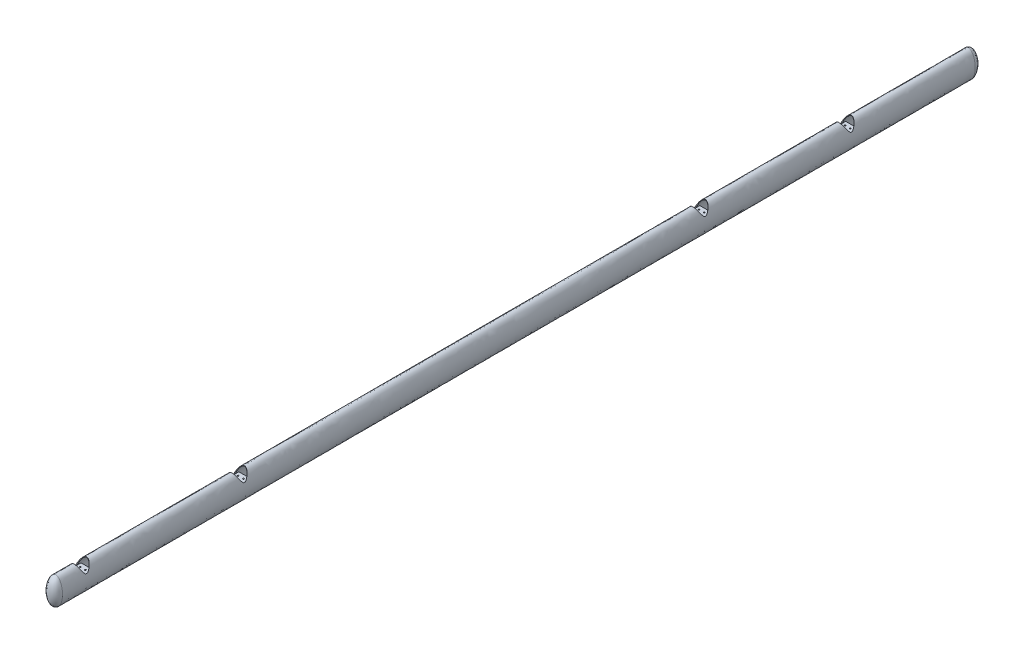
SolidWorks part; units mm, degrees
material "6061 Сплав"
ref_plane "Спереди" through (0, 0, 0) normal (0, 0, 1) x (1, 0, 0)
ref_plane "Сверху" through (0, 0, 0) normal (0, 1, 0) x (1, 0, 0)
ref_plane "Справа" through (0, 0, 0) normal (1, 0, 0) x (0, 0, -1)
sketch "Эскиз1" plane through (0, 0, 0) normal (0, 0, 1) x (1, 0, 0)
  line L0 (0, 286.5014) -> (0, -276.3874) construction
  ellipse E0 centre (234.2877, 0) end of major axis (234.2877, -30) minor radius 15
  ellipse E3 centre (234.2877, 0) end of major axis (234.2877, 28.8) minor radius 13.8
  dimension "D5" = 234.2877
extrude "Бобышка-Вытянуть1" add sketch "Эскиз1" along normal blind 2000
ref_plane "Плоскость1" through (0, 30, 0) normal (0, 1, 0) x (1, 0, 0)
sketch "Эскиз3" plane through (0, 30, 0) normal (0, 1, 0) x (1, 0, 0)
  circle A0 centre (-234.2877, -1946) radius 13.85
  circle A4 centre (234.2877, -270) radius 13.85
  circle A5 centre (234.2877, -590) radius 13.85
  circle A6 centre (234.2877, -1600) radius 13.85
  circle A7 centre (234.2877, -1946) radius 13.85
extrude "Вырез-Вытянуть1" cut sketch "Эскиз3" against normal blind 18
ref_plane "Плоскость2" through (234.2877, 0, 0) normal (1, 0, 0) x (0, 0, -1)
sketch "Эскиз4" plane through (234.2877, 0, 0) normal (1, 0, 0) x (0, 0, -1)
  line L0 (103.9999, 0) -> (-2069.6798, 0) construction
  line L1 (-1613.85, 30) -> (-1932.15, 30) construction
  line L2 (-1959.85, 12) -> (-1931.85, 12)
  line L3 (-1959.85, 12) -> (-1959.85, 8)
  line L4 (-1959.85, 8) -> (-1931.85, 8)
  line L5 (-1931.85, 12) -> (-1931.85, 8)
  line L6 (-1959.85, 30) -> (-1959.85, -38.8491) construction
  line L7 (-1586.15, 30) -> (-1586.15, -17.8904) construction
  line L8 (-603.85, 30) -> (-603.85, -10.0051) construction
  line L10 (-256.15, 30) -> (-256.15, -10.0051) construction
  line L11 (-1614.15, 12) -> (-1586.15, 12)
  line L12 (-1614.15, 12) -> (-1614.15, 8)
  line L13 (-1614.15, 8) -> (-1586.15, 8)
  line L14 (-1586.15, 12) -> (-1586.15, 8)
  line L15 (-603.85, 12) -> (-575.85, 12)
  line L16 (-603.85, 12) -> (-603.85, 8)
  line L17 (-603.85, 8) -> (-575.85, 8)
  line L18 (-575.85, 12) -> (-575.85, 8)
  line L19 (-283.85, 30) -> (-576.15, 30) construction
  line L20 (-284.15, 12) -> (-256.15, 12)
  line L21 (-284.15, 12) -> (-284.15, 8)
  line L22 (-284.15, 8) -> (-256.15, 8)
  line L23 (-256.15, 12) -> (-256.15, 8)
  dimension "D1" = 18
  dimension "D2" = 4
  dimension "D3" = 28
  dimension "D4" = 4
  dimension "D5" = 28
  dimension "D6" = 8
  dimension "D7" = 4
  dimension "D8" = 28
  dimension "D9" = 18
  dimension "D10" = 4
  dimension "D11" = 28
  dimension "D12" = 18
extrude "Бобышка-Вытянуть2" add sketch "Эскиз4" along normal up to next and the other way up to next
sketch3d "Трехмерный эскиз1"
  line L0 (0, 0, 0) -> (0, 0, 781.8375) construction
sketch "Эскиз6" plane through (0, 12, 0) normal (0, 1, 0) x (1, 0, 0)
  line L0 (207.6556, -1946) -> (272.459, -1946) construction
  line L1 (234.2877, -1946) -> (234.2877, -1918.1086) construction
  line L2 (228.6309, -1940.3431) -> (228.6309, -1951.6569) construction
  line L7 (239.9446, -1951.6569) -> (228.6309, -1940.3431) construction
  line L8 (239.9446, -1940.3431) -> (228.6309, -1951.6569) construction
  line L9 (228.6309, -1951.6569) -> (239.9446, -1951.6569) construction
  line L10 (239.9446, -1951.6569) -> (239.9446, -1940.3431) construction
  line L11 (239.9446, -1940.3431) -> (228.6309, -1940.3431) construction
  line L12 (234.2877, -1918.1086) -> (234.2877, 319.955) construction
  line L13 (234.2877, -50) -> (234.2877, 50) construction
  line L15 (234.2877, -1600) -> (234.2877, -1572.1086) construction
  line L16 (228.6309, -1594.3431) -> (228.6309, -1605.6569) construction
  line L17 (239.9446, -1605.6569) -> (228.6309, -1594.3431) construction
  line L18 (239.9446, -1594.3431) -> (228.6309, -1605.6569) construction
  line L19 (228.6309, -1605.6569) -> (239.9446, -1605.6569) construction
  line L20 (239.9446, -1605.6569) -> (239.9446, -1594.3431) construction
  line L21 (239.9446, -1594.3431) -> (228.6309, -1594.3431) construction
  line L22 (234.2877, -590) -> (234.2877, -571.5378) construction
  line L23 (228.6309, -584.3431) -> (228.6309, -595.6569) construction
  line L24 (239.9446, -595.6569) -> (228.6309, -584.3431) construction
  line L25 (239.9446, -584.3431) -> (228.6309, -595.6569) construction
  line L26 (228.6309, -595.6569) -> (239.9446, -595.6569) construction
  line L27 (239.9446, -595.6569) -> (239.9446, -584.3431) construction
  line L28 (239.9446, -584.3431) -> (228.6309, -584.3431) construction
  line L29 (234.2877, -270) -> (234.2877, -258.9739) construction
  line L30 (228.6309, -264.3431) -> (228.6309, -275.6569) construction
  line L31 (239.9446, -275.6569) -> (228.6309, -264.3431) construction
  line L32 (239.9446, -264.3431) -> (228.6309, -275.6569) construction
  line L33 (228.6309, -275.6569) -> (239.9446, -275.6569) construction
  line L34 (239.9446, -275.6569) -> (239.9446, -264.3431) construction
  line L35 (239.9446, -264.3431) -> (228.6309, -264.3431) construction
  arc A0 (248.0355, -1944.32) -> (220.54, -1944.32) centre (234.2877, -1946) ccw construction
  circle A1 centre (228.6309, -1940.3431) radius 1.5
  circle A2 centre (239.9446, -1940.3431) radius 1.5
  circle A3 centre (228.6309, -1951.6569) radius 1.5
  circle A4 centre (239.9446, -1951.6569) radius 1.5
  circle A5 centre (228.6309, -1594.3431) radius 1.5
  circle A6 centre (239.9446, -1594.3431) radius 1.5
  circle A7 centre (228.6309, -1605.6569) radius 1.5
  circle A8 centre (239.9446, -1605.6569) radius 1.5
  circle A9 centre (228.6309, -584.3431) radius 1.5
  circle A10 centre (239.9446, -584.3431) radius 1.5
  circle A11 centre (228.6309, -595.6569) radius 1.5
  circle A12 centre (239.9446, -595.6569) radius 1.5
  circle A13 centre (228.6309, -264.3431) radius 1.5
  circle A14 centre (239.9446, -264.3431) radius 1.5
  circle A15 centre (228.6309, -275.6569) radius 1.5
  circle A16 centre (239.9446, -275.6569) radius 1.5
  point P16 (234.2877, -590)
  point P20 (234.2877, -270)
  point P31 (234.2877, -1600)
  dimension "D3" = 3
  dimension "D5" = 3
  dimension "D7" = 3
  dimension "D9" = 3
  dimension "D1" = 0
  dimension "D2" = 16
  dimension "D4" = 16
  dimension "D6" = 16
  dimension "D8" = 16
extrude "Вырез-Вытянуть2" cut sketch "Эскиз6" against normal through all
sketch "Эскиз7" plane through (0, 0, 2000) normal (0, 0, 1) x (1, 0, 0)
  line L1 (234.2877, -50) -> (234.2877, 50) construction
  line L2 (234.2877, 30) -> (234.2877, 28.8)
  line L3 (234.2877, -28.8) -> (234.2877, -30)
  ellipse E0 centre (234.2877, 0) end of major axis (234.2877, 28.8) minor radius 13.8 (234.2877, -28.8) -> (234.2877, 28.8) ccw
  ellipse E2 centre (234.2877, 0) end of major axis (234.2877, 28.8) minor radius 13.8 construction
  ellipse E3 centre (234.2877, 0) end of major axis (234.2877, 30) minor radius 15 (234.2877, -30) -> (234.2877, 30) ccw
  ellipse E4 centre (234.2877, 0) end of major axis (234.2877, 30) minor radius 15 construction
  point P0 (234.2877, 0)
sketch3d "Трехмерный эскиз2"
  line L0 (234.2877, 30, 2000) -> (234.2877, -43.8, 2000) construction
revolve "Повернуть1" add sketch "Эскиз7" angle 180 about L0
sketch "Эскиз8" plane through (0, 0, 0) normal (0, 0, -1) x (-1, 0, 0)
  line L0 (-234.2877, 30) -> (-234.2877, -43.8) construction
  line L1 (-234.2877, 30) -> (-234.2877, 28.8)
  line L2 (-234.2877, -28.8) -> (-234.2877, -30)
  ellipse E0 centre (-234.2877, 0) end of major axis (-234.2877, 28.8) minor radius 13.8 (-234.2877, -28.8) -> (-234.2877, 28.8) ccw
  ellipse E1 centre (-234.2877, 0) end of major axis (-234.2877, 28.8) minor radius 13.8 construction
  ellipse E2 centre (-234.2877, 0) end of major axis (-234.2877, 28.8) minor radius 13.8 (-234.2877, -28.8) -> (-234.2877, 28.8) ccw construction
  ellipse E3 centre (-234.2877, 0) end of major axis (-234.2877, 30) minor radius 15 (-234.2877, -30) -> (-234.2877, 30) ccw
  ellipse E4 centre (-234.2877, 0) end of major axis (-234.2877, 30) minor radius 15 construction
  point P0 (-234.2877, 0)
sketch3d "Трехмерный эскиз3"
  line L0 (234.2877, 30, 0) -> (234.2877, -39.9503, 0) construction
revolve "Повернуть2" add sketch "Эскиз8" angle 180 about L0
